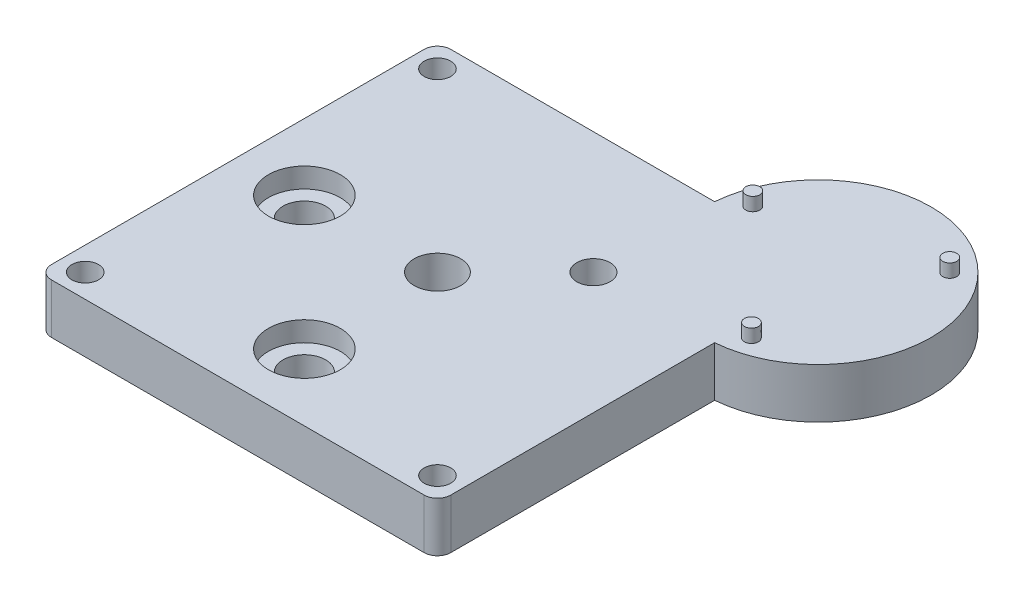
SolidWorks part; units mm, degrees
ref_plane "Front Plane" through (0, 0, 0) normal (0, 0, 1) x (1, 0, 0)
ref_plane "Top Plane" through (0, 0, 0) normal (0, 1, 0) x (1, 0, 0)
ref_plane "Right Plane" through (0, 0, 0) normal (1, 0, 0) x (0, 0, -1)
sketch "Sketch1" plane through (0, 0, 0) normal (0, 1, 0) x (1, 0, 0)
  line L0 (-38.1, -38.1) -> (56.218, 56.218) construction
  line L1 (-38.1, 38.1) -> (38.1, 38.1)
  line L2 (-38.1, 38.1) -> (-38.1, -38.1)
  line L3 (-38.1, -38.1) -> (38.1, -38.1)
  line L4 (38.1, 38.1) -> (38.1, -38.1)
  line L5 (-38.1, 38.1) -> (38.1, -38.1) construction
  line L6 (-38.1, -38.1) -> (38.1, 38.1) construction
  point P0 (0, 0)
  dimension "D1" = 76.2
extrude "Boss-Extrude1" add sketch "Sketch1" along normal blind 9.525
sketch "Sketch6" plane through (0, 0, 0) normal (0, 1, 0) x (1, 0, 0)
  line L0 (38.1, 38.1) -> (-38.1, 38.1) construction
  line L1 (-38.1, 38.1) -> (-38.1, -38.1) construction
  line L2 (38.1, -38.1) -> (38.1, 38.1) construction
  line L3 (-38.1, -38.1) -> (38.1, -38.1) construction
  circle A0 centre (-27.3237, 27.3237) radius 3.81
  circle A1 centre (27.3237, -27.3237) radius 3.81
  dimension "D2" = 7.62
  dimension "D7" = 15.24
  dimension "D1" = 10.7763
  dimension "D3" = 10.7763
  dimension "D4" = 10.7763
  dimension "D5" = 10.7763
  dimension "D6" = 15.24
extrude "Cut-Extrude2" cut sketch "Sketch6" along direction (0, 1, 0) on the side of the normal blind 2.54 draft 30
sketch "Sketch7" plane through (0, 0, 0) normal (0, 1, 0) x (1, 0, 0)
  line L2 (-38.1, 38.1) -> (-38.1, -38.1) construction
  line L3 (-38.1, -38.1) -> (38.1, -38.1) construction
  circle A0 centre (-27.94, -27.94) radius 4.445
  dimension "D3" = 8.89
  dimension "D2" = 10.16
  dimension "D1" = 10.16
sketch "Sketch12" plane through (0, 9.525, 0) normal (0, 1, 0) x (1, 0, 0)
  line L2 (-38.1, -38.1) -> (38.1, -38.1) construction
  line L3 (-38.1, 38.1) -> (-38.1, -38.1) construction
  circle A0 centre (-25.4, 0) radius 4.064
  circle A1 centre (0, -25.4) radius 4.064
  dimension "D2" = 12.7
  dimension "D3" = 8.128
  dimension "D4" = 38.1
  dimension "D5" = 12.7
  dimension "D1" = 38.1
extrude "Cut-Extrude4" cut sketch "Sketch12" against normal up to next
sketch "Sketch13" plane through (0, 9.525, 0) normal (0, -1, 0) x (1, 0, 0)
  circle A0 centre (0, 25.4) radius 4.064 construction
  circle A1 centre (-25.4, 0) radius 4.064 construction
  circle A6 centre (-25.4, 0) radius 6.858
  circle A9 centre (0, 25.4) radius 6.858
  dimension "D1" = 13.716
  dimension "D2" = 13.716
extrude "Cut-Extrude7" cut sketch "Sketch13" along normal blind 3.81
extrude "Cut-Extrude8" cut sketch "Sketch7" along normal blind 3.81 draft 45
ref_axis "Axis1" through (0, -9.5852, 25.4) along (0, 1, 0)
ref_axis "Axis2" through (-25.4, -15.4165, 0) along (0, 1, 0)
sketch "Sketch15" plane through (0, 9.525, 0) normal (0, 1, 0) x (1, 0, 0)
  circle A4 centre (0, 0) radius 4.445
  dimension "D1" = 8.89
extrude "Cut-Extrude9" cut sketch "Sketch15" against normal up to next
fillet "Fillet1" radius 2.54 4 edges at (38.1, 4.7625, -38.1) (38.1, 4.7625, 38.1) (-38.1, 4.7625, 38.1) (-38.1, 4.7625, -38.1)
sketch "Sketch17" plane through (0, 9.525, 0) normal (0, 1, 0) x (1, 0, 0)
  line L0 (38.1, -35.56) -> (38.1, 35.56) construction
  line L1 (35.56, 38.1) -> (-35.56, 38.1) construction
  circle A0 centre (36.3113, 36.3113) radius 21.59
  point P5 (36.3113, 36.3113)
  dimension "D1" = 43.18
  dimension "D2" = 1.7887
  dimension "D3" = 1.7887
extrude "Boss-Extrude2" add sketch "Sketch17" against normal up to surface (9.525 mm away) up to face at (0, 0, 4.445)
sketch "Sketch18" plane through (0, 9.525, 0) normal (0, 1, 0) x (1, 0, 0)
  line L0 (-38.1, 35.56) -> (-38.1, -35.56) construction
  circle A0 centre (19.1663, 41.0207) radius 1.3335
  circle A2 centre (48.9622, 48.8046) radius 1.3335
  circle A3 centre (40.8053, 19.1086) radius 1.3335
  point P10 (36.3113, 36.3113)
  dimension "D1" = 2.667
  dimension "D2" = 17.78
  dimension "D4" = 57.2663
  dimension "D5" = 74.4113
  dimension "D6" = 78.9053
  dimension "D3" = 3
extrude "Boss-Extrude3" add sketch "Sketch18" along normal blind 2.54
sketch "Sketch19" plane through (0, 9.525, 0) normal (0, 1, 0) x (1, 0, 0)
  circle A0 centre (36.3113, 36.3113) radius 21.59 construction
  arc A1 (38.1, 14.7955) -> (14.7955, 38.1) centre (36.3113, 36.3113) ccw construction
sketch "Sketch20" plane through (0, 9.525, 0) normal (0, 1, 0) x (1, 0, 0)
  line L0 (-38.1, -38.1) -> (56.218, 56.218) construction
  line L1 (-38.1, 38.1) -> (38.1, -38.1) construction
  circle A0 centre (-33.6099, -33.6099) radius 2.54
  circle A2 centre (33.6099, -33.6099) radius 2.54
  circle A3 centre (-33.6099, 33.6099) radius 2.54
  circle A4 centre (14.8835, 14.8835) radius 3.175
  dimension "D1" = 5.08
  dimension "D4" = 5.08
  dimension "D5" = 5.08
  dimension "D7" = 6.35
  dimension "D2" = 6.35
  dimension "D3" = 6.35
  dimension "D6" = 6.35
  dimension "D8" = 68.58
  dimension "D9" = 51.9835
  dimension "D10" = 51.9835
  dimension "D11" = 67.2197
  dimension "D12" = 67.2197
extrude "Cut-Extrude10" cut sketch "Sketch20" against normal up to next
